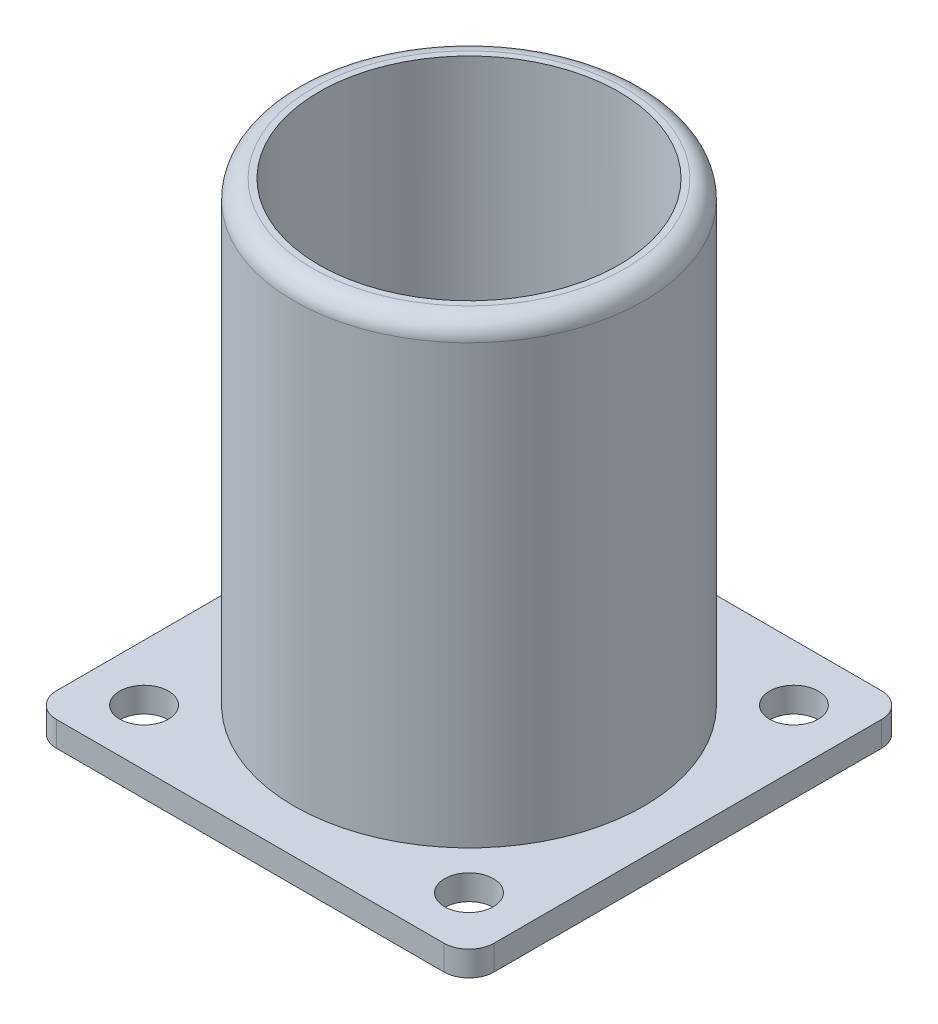
SolidWorks part; units mm, degrees
ref_plane "Plano frontal" through (0, 0, 0) normal (0, 0, 1) x (1, 0, 0)
ref_plane "Plano superior" through (0, 0, 0) normal (0, 1, 0) x (1, 0, 0)
ref_plane "Plano direito" through (0, 0, 0) normal (1, 0, 0) x (0, 0, -1)
sketch "Esboço1" plane through (0, 0, 0) normal (0, 1, 0) x (1, 0, 0)
  line L0 (0, 0) -> (17.5, 0) construction
  line L1 (-17.5, -17.5) -> (17.5, -17.5)
  line L2 (-17.5, -17.5) -> (-17.5, 17.5)
  line L3 (-17.5, 17.5) -> (17.5, 17.5)
  line L4 (17.5, -17.5) -> (17.5, 17.5)
  line L5 (-17.5, -17.5) -> (17.5, 17.5) construction
  line L6 (-17.5, 17.5) -> (17.5, -17.5) construction
  line L7 (-17.5, -13) -> (-13, -13) construction
  line L8 (-17.5, -13) -> (-17.5, -17.5) construction
  line L9 (-17.5, -17.5) -> (-13, -17.5) construction
  line L10 (-13, -13) -> (-13, -17.5) construction
  line L11 (-17.5, -13) -> (-13, -17.5) construction
  line L12 (-17.5, -17.5) -> (-13, -13) construction
  line L13 (0, 0) -> (0, -17.5) construction
  line L14 (0, 0) -> (0, 17.5) construction
  line L15 (-0.75, -11.9765) -> (-0.75, 12)
  line L16 (-12, -12) -> (-11.3259, -12) construction
  line L17 (-12, -12) -> (-12, 12) construction
  line L18 (-12, 12) -> (-0.75, 12) construction
  line L19 (12, -12) -> (12, 12) construction
  line L20 (-12, -12) -> (12, 12) construction
  line L21 (-12, 12) -> (12, -12) construction
  line L22 (0.75, -11.9765) -> (0.75, 12)
  line L23 (0.75, 0) -> (0.75, 17.5) construction
  line L24 (-0.75, 0) -> (-0.75, 17.5) construction
  line L25 (0.75, 12) -> (0.75, 17.5) construction
  line L26 (-0.75, 12) -> (-0.75, 17.5) construction
  line L27 (0.75, -11.9765) -> (0.75, 12)
  line L28 (2.25, -11.9765) -> (2.25, 12)
  line L29 (2.25, -11.9765) -> (2.25, 12)
  line L30 (3.75, -11.9765) -> (3.75, 12)
  line L31 (3.75, -11.9765) -> (3.75, 12)
  line L32 (5.25, -11.9765) -> (5.25, 12)
  line L33 (5.25, -11.9765) -> (5.25, 12)
  line L34 (6.75, -11.9765) -> (6.75, 12)
  line L35 (6.75, -11.9765) -> (6.75, 12)
  line L36 (8.25, -11.9765) -> (8.25, 12)
  line L37 (8.25, -11.9765) -> (8.25, 12)
  line L38 (9.75, -11.9765) -> (9.75, 12)
  line L39 (9.75, -11.9765) -> (9.75, 12)
  line L40 (11.25, -11.9765) -> (11.25, 12)
  line L41 (0, -11.9765) -> (0.75, -11.9765) construction
  line L42 (0, 12) -> (0.75, 12) construction
  line L43 (0.75, 12) -> (12, 12) construction
  line L44 (-0.75, 12) -> (0, 12) construction
  line L45 (-11.3259, -12) -> (0, -12) construction
  line L46 (0, -12) -> (12, -12) construction
  line L47 (-0.75, -11.9765) -> (0, -11.9765) construction
  line L48 (-11.25, -11.9765) -> (-11.25, 12)
  line L49 (-9.75, -11.9765) -> (-9.75, 12)
  line L50 (-8.25, -11.9765) -> (-8.25, 12)
  line L51 (-6.75, -11.9765) -> (-6.75, 12)
  line L52 (-5.25, -11.9765) -> (-5.25, 12)
  line L53 (-3.75, -11.9765) -> (-3.75, 12)
  line L54 (-2.25, -11.9765) -> (-2.25, 12)
  circle A0 centre (-13, -13) radius 1.95
  circle A1 centre (13, -13) radius 1.95
  circle A2 centre (13, 13) radius 1.95
  circle A3 centre (-13, 13) radius 1.95
  arc A4 (-0.75, 11.9765) -> (-2.25, 11.7872) centre (0, 0) ccw
  arc A5 (0.75, 11.9765) -> (0, 12) centre (0, 0) ccw construction
  arc A6 (0, 12) -> (-0.75, 11.9765) centre (0, 0) ccw construction
  arc A7 (-0.75, -11.9765) -> (0, -12) centre (0, 0) ccw construction
  arc A8 (0, -12) -> (2.25, -11.7872) centre (0, 0) ccw
  arc A9 (2.25, -11.7872) -> (3.75, -11.399) centre (0, 0) ccw construction
  arc A10 (3.75, -11.399) -> (5.25, -10.7906) centre (0, 0) ccw
  arc A11 (3.75, 11.399) -> (2.25, 11.7872) centre (0, 0) ccw construction
  arc A12 (2.25, 11.7872) -> (0.75, 11.9765) centre (0, 0) ccw
  arc A13 (6.75, 9.9216) -> (5.25, 10.7906) centre (0, 0) ccw construction
  arc A14 (5.25, 10.7906) -> (3.75, 11.399) centre (0, 0) ccw
  arc A15 (5.25, -10.7906) -> (6.75, -9.9216) centre (0, 0) ccw construction
  arc A16 (6.75, -9.9216) -> (8.4853, -8.4853) centre (0, 0) ccw
  arc A17 (9.75, 6.9955) -> (8.4853, 8.4853) centre (0, 0) ccw construction
  arc A18 (8.4853, 8.4853) -> (6.75, 9.9216) centre (0, 0) ccw
  arc A19 (8.4853, -8.4853) -> (9.75, -6.9955) centre (0, 0) ccw construction
  arc A20 (9.75, -6.9955) -> (11.25, -4.1758) centre (0, 0) ccw
  arc A21 (12, 0) -> (11.25, 4.1758) centre (0, 0) ccw construction
  arc A22 (11.25, 4.1758) -> (9.75, 6.9955) centre (0, 0) ccw
  arc A23 (11.25, -4.1758) -> (12, 0) centre (0, 0) ccw construction
  arc A24 (-2.25, 11.7872) -> (-3.75, 11.399) centre (0, 0) ccw construction
  arc A25 (-3.75, 11.399) -> (-5.25, 10.7906) centre (0, 0) ccw
  arc A26 (-3.75, -11.399) -> (-2.25, -11.7872) centre (0, 0) ccw construction
  arc A27 (-2.25, -11.7872) -> (-0.75, -11.9765) centre (0, 0) ccw
  arc A28 (-6.75, -9.9216) -> (-5.25, -10.7906) centre (0, 0) ccw construction
  arc A29 (-5.25, -10.7906) -> (-3.75, -11.399) centre (0, 0) ccw
  arc A30 (-5.25, 10.7906) -> (-6.75, 9.9216) centre (0, 0) ccw construction
  arc A31 (-6.75, 9.9216) -> (-8.4853, 8.4853) centre (0, 0) ccw
  arc A32 (-8.4853, 8.4853) -> (-9.75, 6.9955) centre (0, 0) ccw construction
  arc A33 (-9.75, 6.9955) -> (-11.25, 4.1758) centre (0, 0) ccw
  arc A34 (-9.75, -6.9955) -> (-8.4853, -8.4853) centre (0, 0) ccw construction
  arc A35 (-8.4853, -8.4853) -> (-6.75, -9.9216) centre (0, 0) ccw
  arc A36 (-12, 0) -> (-11.25, -4.1758) centre (0, 0) ccw construction
  arc A37 (-11.25, -4.1758) -> (-9.75, -6.9955) centre (0, 0) ccw
  arc A38 (-11.25, 4.1758) -> (-12, 0) centre (0, 0) ccw construction
  point P0 (0, 0)
  point P6 (-15.25, -15.25)
  dimension "D3" = 3.9
  dimension "D4" = 24
  dimension "D1" = 35
  dimension "D2" = 4.5
  dimension "D8" = 1.5
  dimension "D5" = 0.75
  dimension "D6" = 0.75
  dimension "D7" = 8
extrude "Ressalto-extrusão1" add sketch "Esboço1" along normal blind 2 contours L1 L4 L3 L2 A22 A2 L40 A1 A20 L39 A18 L37 A16 L35 A14 L33 A10 L31 A12 region at (0, 0, 0)
ref_plane "Plano1" through (0, 2, 0) normal (0, 1, 0) x (1, 0, 0)
fillet "Filete2" radius 2 4 edges at (-17.5, 1, 17.5) (17.5, 1, 17.5) (17.5, 1, -17.5) (-17.5, 1, -17.5)
sketch "Esboço3" plane through (0, 2, 0) normal (0, 1, 0) x (1, 0, 0)
  circle A0 centre (0, 0) radius 12
  arc A1 (-0.75, 11.9765) -> (-2.25, 11.7872) centre (0, 0) ccw construction
  circle A2 centre (0, 0) radius 14
  dimension "D1" = 2
extrude "Ressalto-extrusão3" add sketch "Esboço3" along normal blind 36.5
fillet "Filete3" radius 1.5 1 edges at (0, 38.5, 14)
equation "\"D6@Esboço1\"=\"D5@Esboço1\""
